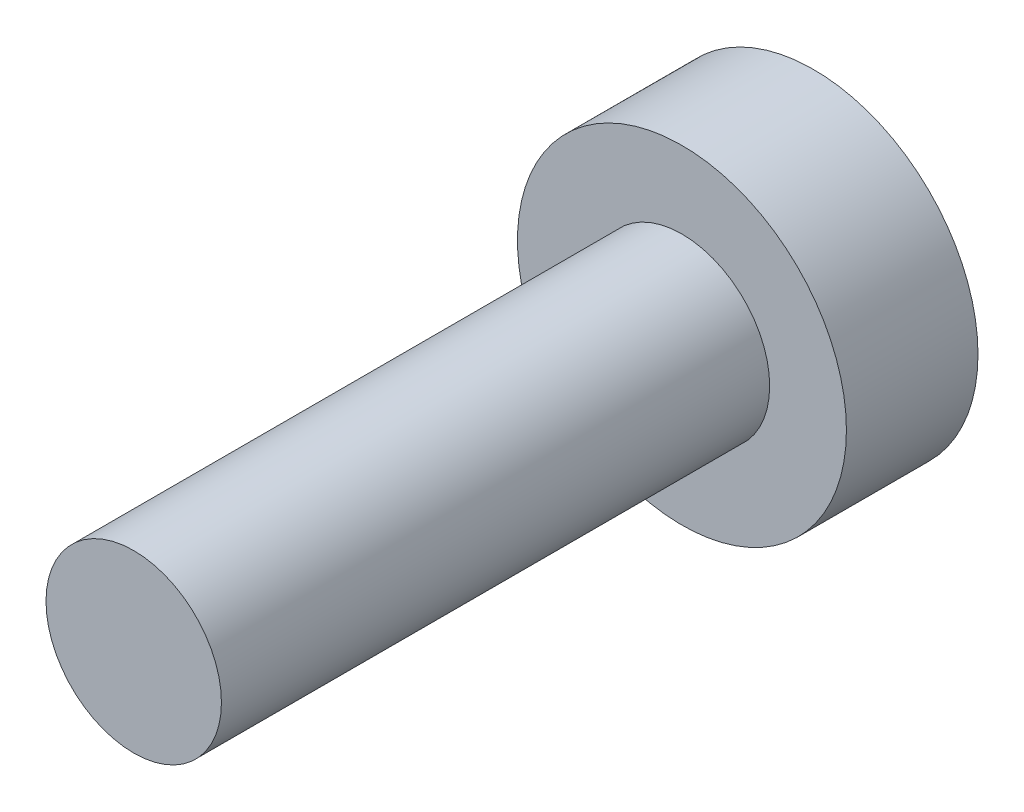
SolidWorks part; units mm, degrees
ref_plane "Ebene vorne (XY)" through (0, 0, 0) normal (0, 0, 1) x (1, 0, 0)
ref_plane "Ebene oben  (XZ)" through (0, 0, 0) normal (0, 1, 0) x (1, 0, 0)
ref_plane "Ebene rechts  (YZ)" through (0, 0, 0) normal (1, 0, 0) x (0, 0, -1)
ref_axis "x-Achse" through (-1.65, 0, 0) along (1, 0, 0)
ref_axis "y-Achse" through (0, 1.65, 0) along (0, -1, 0)
ref_axis "z-Achse" through (0, 0, -1.51) along (0, 0, 1)
sketch "Profile_Shank_1p6_length_5" plane through (0, 0, 0) normal (0, 0, 1) x (1, 0, 0)
  circle A0 centre (0, 0) radius 0.8
extrude "Shank_1p6_length_5" add sketch "Profile_Shank_1p6_length_5" along normal blind 5
sketch "Profile_Head_d3_height_1p2" plane through (0, 0, 0) normal (0, 0, 1) x (1, 0, 0)
  circle A0 centre (0, 0) radius 1.5
extrude "Head_d3_height_1p2" add sketch "Profile_Head_d3_height_1p2" against normal blind 1.2
